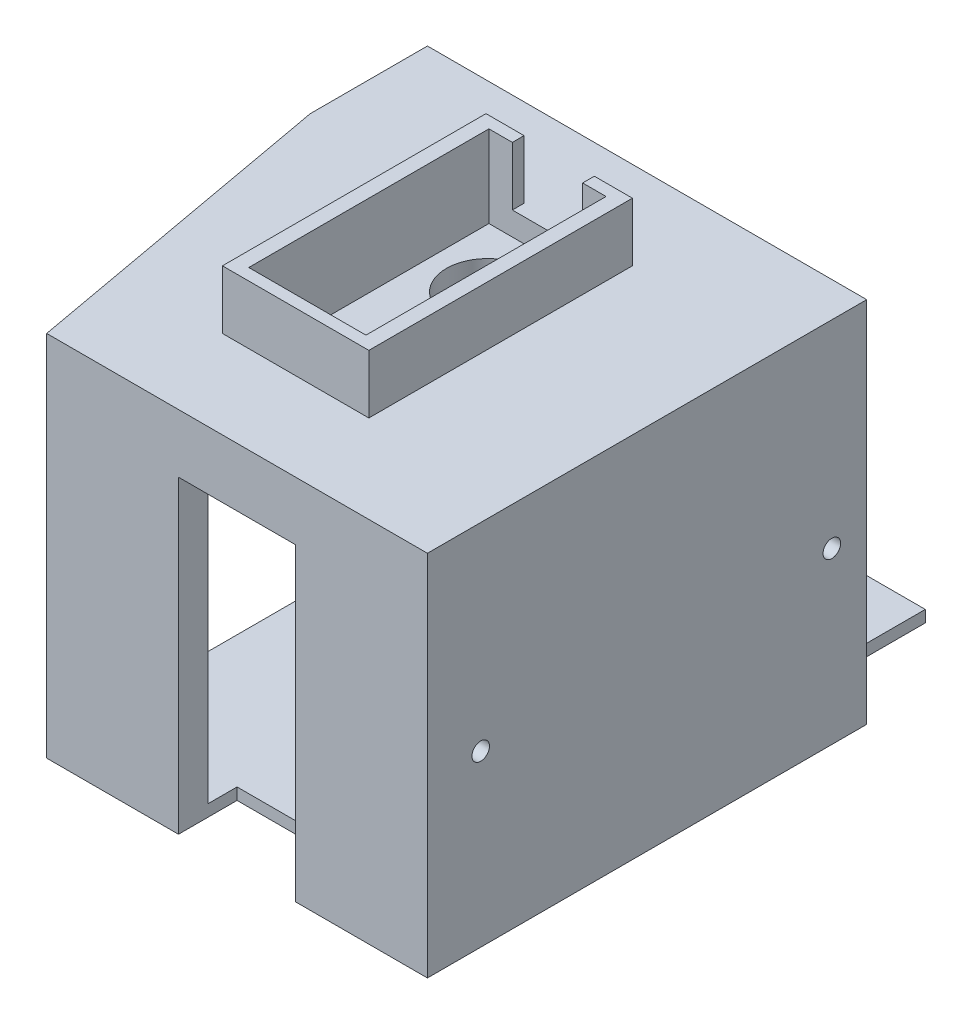
SolidWorks part; units mm, degrees
ref_plane "Front Plane" through (0, 0, 0) normal (0, 0, 1) x (1, 0, 0)
ref_plane "Top Plane" through (0, 0, 0) normal (0, 1, 0) x (1, 0, 0)
ref_plane "Right Plane" through (0, 0, 0) normal (1, 0, 0) x (0, 0, -1)
sketch "Sketch1" plane through (0, 0, 0) normal (0, 1, 0) x (1, 0, 0)
  line L1 (0, 0) -> (55, 0)
  line L2 (0, 0) -> (0, 65)
  line L3 (0, 65) -> (55, 65)
  line L4 (55, 0) -> (55, 65)
  dimension "D1" = 55
  dimension "D2" = 65
extrude "Base" add sketch "Sketch1" along normal blind 2
sketch "Sketch2" plane through (0, 2, 0) normal (0, 1, 0) x (1, 0, 0)
  line L0 (0, 0) -> (55, 0) construction
  line L2 (55, 65) -> (0, 65) construction
  circle A0 centre (3, 3.5) radius 1.125
  circle A1 centre (52, 3.5) radius 1.125
  circle A2 centre (3, 61.5) radius 1.125
  circle A3 centre (52, 61.5) radius 1.125
  point P12 (27.5, 0)
  dimension "D1" = 2.25
  dimension "D2" = 24.5
  dimension "D3" = 24.5
  dimension "D4" = 58
  dimension "D5" = 3.5
extrude "PiMountScrewHoles" cut sketch "Sketch2" against normal up to surface (2 mm away) up to face at (27.5, 0, -32.5)
sketch "Sketch3" plane through (0, 0, 0) normal (-1, 0, 0) x (0, 0, 1)
  line L0 (-65, 0) -> (0, 0) construction
  line L1 (-65, 2) -> (-45, 2)
  line L2 (-65, 2) -> (-65, 0)
  line L3 (-65, 0) -> (-45, 0)
  line L4 (-45, 2) -> (-45, 0)
  dimension "D1" = 20
extrude "PlateLegExt-1" add sketch "Sketch3" along normal blind 10
sketch "Sketch19" plane through (0, 0, -65) normal (0, 0, -1) x (-1, 0, 0)
  line L1 (-55, 2) -> (0, 2)
  line L2 (-55, 2) -> (-55, 0)
  line L3 (-55, 0) -> (0, 0)
  line L4 (0, 2) -> (0, 0)
extrude "PiFrontBase" add sketch "Sketch19" along normal blind 20
sketch "Sketch21" plane through (55, 0, 0) normal (1, 0, 0) x (0, 0, -1)
  line L0 (0, 0) -> (85, 0) construction
  line L1 (0, 2) -> (65, 2)
  line L2 (0, 2) -> (0, 0)
  line L3 (0, 0) -> (65, 0)
  line L4 (65, 2) -> (65, 0)
extrude "BatteryWall-Ext" add sketch "Sketch21" along normal blind 10
sketch "Sketch22" plane through (0, 0, 0) normal (0, 0, 1) x (1, 0, 0)
  line L0 (0, 0) -> (65, 0) construction
  line L1 (0, 2) -> (22.5, 2)
  line L2 (0, 2) -> (0, 0)
  line L3 (0, 0) -> (22.5, 0)
  line L4 (22.5, 2) -> (22.5, 0)
  line L6 (42.5, 2) -> (55, 2)
  line L7 (42.5, 2) -> (42.5, 0)
  line L8 (42.5, 0) -> (55, 0)
  line L11 (0, 2) -> (65, 2) construction
  line L12 (55, 2) -> (55, 0)
  line L13 (55, 0) -> (55, 2) construction
  point P16 (32.5, 0)
  dimension "D1" = 10
  dimension "D2" = 20
extrude "PlateLegExt-2" add sketch "Sketch22" along normal blind 10
sketch "Sketch30" plane through (55, 0, 0) normal (1, 0, 0) x (0, 0, -1)
  line L1 (-10, 2) -> (0, 2)
  line L2 (-10, 2) -> (-10, 0)
  line L3 (-10, 0) -> (0, 0)
  line L4 (0, 2) -> (0, 0)
extrude "CornerExtension" add sketch "Sketch30" along normal up to vertex (10 mm away) up to point (65, 2, 0)
sketch "Sketch23" plane through (0, 2, 0) normal (0, 1, 0) x (1, 0, 0)
  line L0 (65, 65) -> (55, 65) construction
  line L2 (22.5, -5) -> (0, -5)
  line L3 (22.5, -5) -> (22.5, -10)
  line L4 (-5, 65) -> (-10, 65)
  line L8 (60, 65) -> (65, 65)
  line L9 (60, 65) -> (60, -5)
  line L11 (65, 65) -> (65, -10)
  line L14 (-5, 65) -> (-5, 45)
  line L15 (-5, 45) -> (-10, 45)
  line L16 (-10, 65) -> (-10, 45)
  line L21 (22.5, -10) -> (0, -10)
  line L22 (0, -5) -> (0, -10)
  line L23 (22.5, -10) -> (22.5, 0) construction
  line L24 (0, 65) -> (-10, 65) construction
  line L25 (42.5, -10) -> (42.5, 0) construction
  line L26 (42.5, -10) -> (65, -10)
  line L27 (42.5, -10) -> (42.5, -5)
  line L30 (65, 65) -> (65, -10) construction
  line L31 (65, -10) -> (42.5, -10) construction
  line L32 (42.5, -5) -> (60, -5)
extrude "PlateLegs" add sketch "Sketch23" along normal blind 50.8
sketch "Sketch29" plane through (65, 0, 0) normal (1, 0, 0) x (0, 0, -1)
  line L0 (-10, 0) -> (65, 0) construction
  circle A0 centre (59.045, 29) radius 1.5
  circle A1 centre (-0.905, 29) radius 1.5
  point P8 (27.5, 0)
  dimension "D1" = 3
  dimension "D2" = 59.95
  dimension "D3" = 31.545
  dimension "D4" = 29
extrude "Battery-ScrewHoles" cut sketch "Sketch29" against normal up to surface (5 mm away) up to face at (60, 27.4, -30)
sketch "Sketch24" plane through (0, 52.8, 0) normal (0, 1, 0) x (1, 0, 0)
  line L7 (0, -10) -> (65, -10)
  line L8 (42.5, -10) -> (65, -10) construction
  line L9 (65, -10) -> (65, 65)
  line L10 (65, 65) -> (-10, 65)
  line L11 (-10, 65) -> (-10, 45)
  line L12 (-10, 45) -> (0, -10)
extrude "RotatorPlate" add sketch "Sketch24" along normal blind 10
sketch "Sketch25" plane through (0, 62.8, 0) normal (0, 1, 0) x (1, 0, 0)
  line L2 (37.5, 7) -> (37.5, 48)
  line L4 (17.5, 7) -> (17.5, 48)
  line L7 (37.5, 48) -> (17.5, 48)
  line L8 (17.5, 7) -> (37.5, 7)
  line L9 (65, -10) -> (65, 65) construction
  line L11 (65, 65) -> (-10, 65) construction
  point P8 (27.5, 65)
  point P9 (65, 27.5)
  point P10 (37.5, 27.5)
  point P11 (27.5, 48)
  dimension "D1" = 41
  dimension "D2" = 20
extrude "Inset-Servo" cut sketch "Sketch25" against normal blind 4
sketch "Sketch26" plane through (0, 58.8, 0) normal (0, 1, 0) x (1, 0, 0)
  line L3 (37.5, 48) -> (17.5, 48) construction
  circle A0 centre (27.5, 37.75) radius 1.5
  point P8 (27.5, 48)
  dimension "D1" = 3
  dimension "D2" = 10.25
extrude "Hole-ServoScrew" cut sketch "Sketch26" against normal up to surface (6 mm away) up to face at (20.9091, 52.8, -15.4545)
sketch "Sketch27" plane through (0, 58.8, 0) normal (0, 1, 0) x (1, 0, 0)
  circle A0 centre (27.5, 37.75) radius 7
  circle A1 centre (27.5, 37.75) radius 1.5 construction
  dimension "D1" = 14
extrude "Inset-ServoAxle" cut sketch "Sketch27" against normal blind 5.8
sketch "Sketch28" plane through (0, 62.8, 0) normal (0, 1, 0) x (1, 0, 0)
  line L0 (37.5, 48) -> (33.5, 48)
  line L1 (37.5, 7) -> (17.5, 7)
  line L2 (37.5, 7) -> (37.5, 48)
  line L4 (17.5, 7) -> (17.5, 48)
  line L5 (40, 5) -> (15, 5)
  line L6 (40, 5) -> (40, 50)
  line L8 (15, 5) -> (15, 50)
  line L9 (37.5, 48) -> (17.5, 48) construction
  line L10 (17.5, 48) -> (21.5, 48)
  line L11 (37.5, 7) -> (37.5, 48) construction
  line L12 (33.5, 48) -> (33.5, 50)
  line L13 (33.5, 50) -> (40, 50)
  line L14 (21.5, 48) -> (21.5, 50)
  line L15 (21.5, 50) -> (15, 50)
  line L16 (37.5, 48) -> (17.5, 48) construction
  line L17 (17.5, 7) -> (37.5, 7) construction
  line L18 (17.5, 48) -> (17.5, 7) construction
  point P15 (27.5, 7)
  point P19 (27.5, 5)
  point P20 (40, 27.5)
  point P21 (37.5, 27.5)
  point P28 (27.5, 48)
  point P29 (21.5, 49)
  dimension "D1" = 6
  dimension "D2" = 12
  dimension "D3" = 45
  dimension "D4" = 25
extrude "RetainingWalls-Servo" add sketch "Sketch28" along normal blind 10
equation "\"PlateLegExtent\"= 10mm"
equation "\"D1@PlateLegExt-1\" = \"PlateLegExtent\""
equation "\"PlateLegHeight\"= 2in"
equation "\"D1@BatteryWall-Ext\" = \"PlateLegExtent\""
equation "\"D1@PlateLegExt-2\" = \"PlateLegExtent\""
equation "\"D1@PlateLegs\" = \"PlateLegHeight\""
